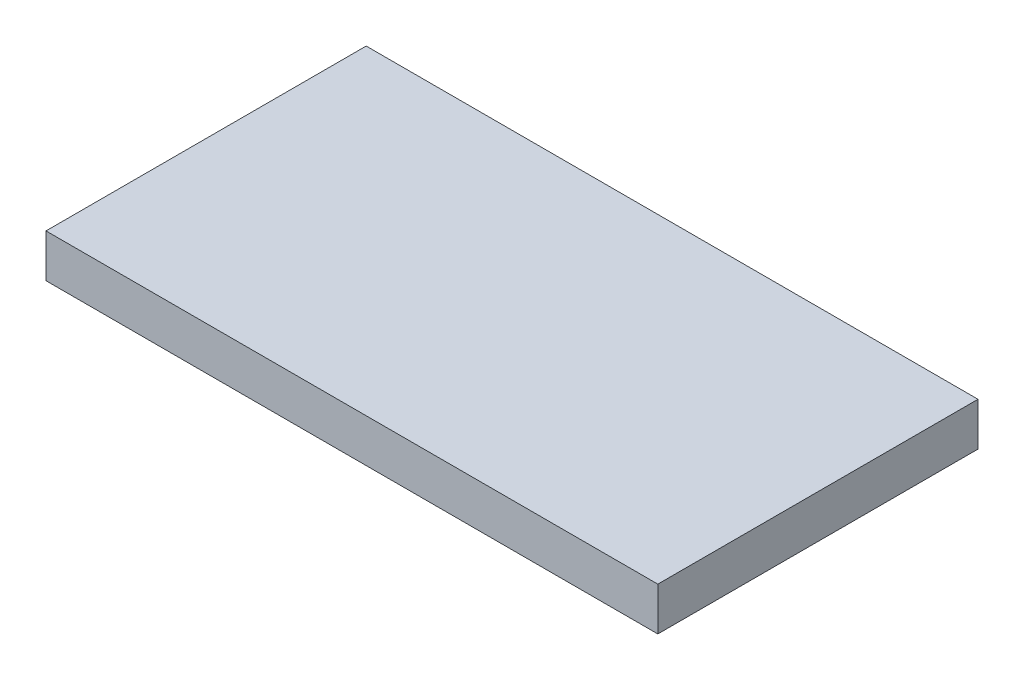
SolidWorks part; units mm, degrees
ref_plane "Front Plane" through (0, 0, 0) normal (0, 0, 1) x (1, 0, 0)
ref_plane "Top Plane" through (0, 0, 0) normal (0, 1, 0) x (1, 0, 0)
ref_plane "Right Plane" through (0, 0, 0) normal (1, 0, 0) x (0, 0, -1)
sketch "Sketch1" plane through (0, 0, 0) normal (0, 1, 0) x (1, 0, 0)
  line L1 (-45, 23.55) -> (45, 23.55)
  line L2 (-45, 23.55) -> (-45, -23.55)
  line L3 (-45, -23.55) -> (45, -23.55)
  line L4 (45, 23.55) -> (45, -23.55)
  point P4 (0, 23.55)
  point P5 (45, 0)
  dimension "D1" = 47.1
  dimension "D2" = 90
extrude "Boss-Extrude1" add sketch "Sketch1" along normal blind 6.35
